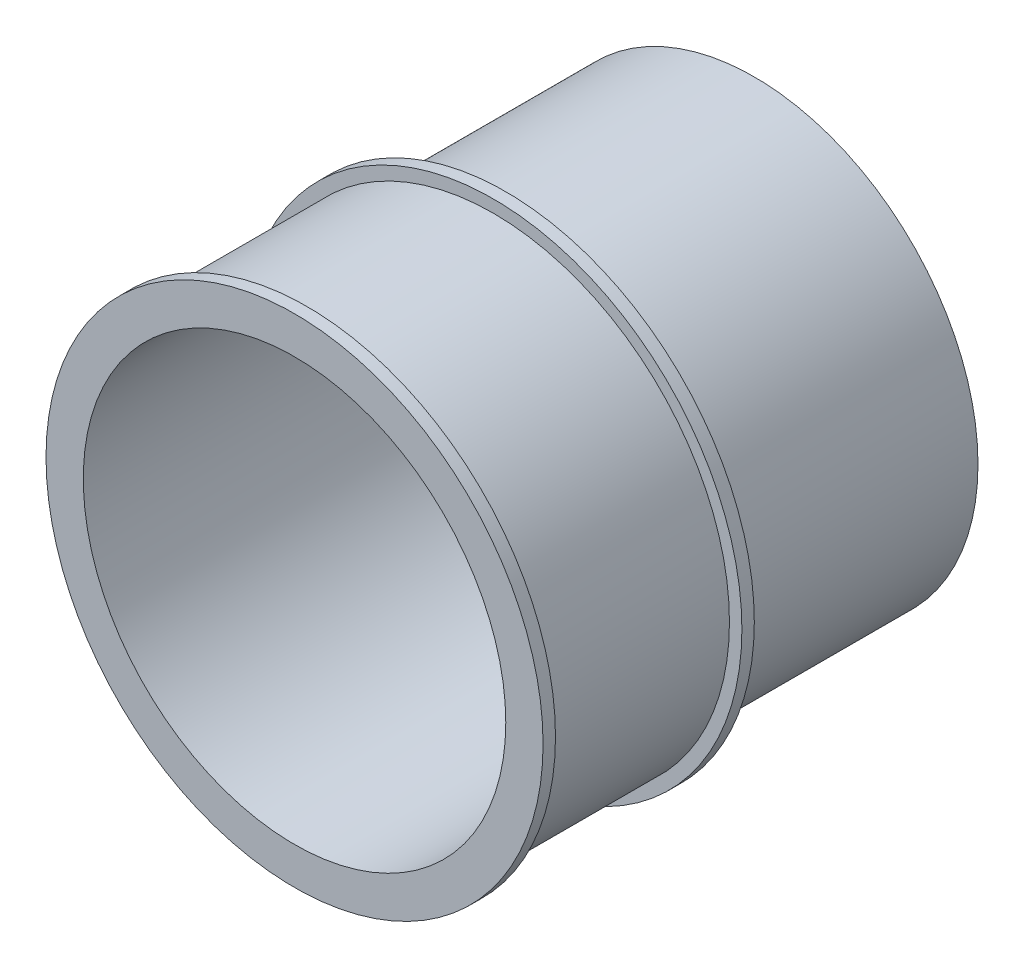
SolidWorks part; units mm, degrees
ref_plane "前视基准面" through (0, 0, 0) normal (0, 0, 1) x (1, 0, 0)
ref_plane "上视基准面" through (0, 0, 0) normal (0, 1, 0) x (1, 0, 0)
ref_plane "右视基准面" through (0, 0, 0) normal (1, 0, 0) x (0, 0, -1)
other "Configuration Table"
sketch "草图1" plane through (0, 0, 0) normal (0, 0, 1) x (1, 0, 0)
  circle A0 centre (0, 0) radius 38
  circle A1 centre (0, 0) radius 36
  dimension "D1" = 2
extrude "凸台-拉伸1" add sketch "草图1" along normal blind 34
sketch "草图2" plane through (0, 0, 34) normal (0, 0, 1) x (1, 0, 0)
  circle A1 centre (0, 0) radius 38 construction
  circle A2 centre (0, 0) radius 40
  circle A3 centre (0, 0) radius 40
  circle A4 centre (0, 0) radius 38
  dimension "D1" = 2
extrude "凸台-拉伸2" add sketch "草图2" against normal blind 2
extrude "凸台-拉伸3" add sketch "草图2<2>" along normal blind 2 from surface starting at face at (38, 0, 0)
sketch "草图2<2>" plane through (0, 0, 34) normal (0, 0, 1) x (1, 0, 0) same geometry as "草图2"
sketch "草图3" plane through (0, 0, 0) normal (0, 0, -1) x (-1, 0, 0)
  circle A1 centre (0, 0) radius 36 construction
  circle A2 centre (0, 0) radius 34
  circle A3 centre (0, 0) radius 34
  circle A4 centre (0, 0) radius 36
  dimension "D1" = 2
extrude "凸台-拉伸4" add sketch "草图3" along normal blind 40 separate body
sketch "草图4" plane through (0, 0, -40) normal (0, 0, -1) x (-1, 0, 0)
  circle A0 centre (0, 0) radius 34 construction
  circle A1 centre (0, 0) radius 34
extrude "凸台-拉伸5" add sketch "草图4" against normal blind 2
sketch "草图5" plane through (0, 0, -40) normal (0, 0, -1) x (-1, 0, 0)
  circle A0 centre (0, 0) radius 5
extrude "切除-拉伸1" cut sketch "草图5" against normal through all both
sketch "草图6" plane through (0, 0, 0) normal (0, 0, 1) x (1, 0, 0)
  circle A0 centre (0, 0) radius 34 construction
  circle A1 centre (0, 0) radius 34
extrude "凸台-拉伸6" add sketch "草图6" along normal blind 2 from offset 30 offset against normal yes
sketch "草图7" plane through (0, 0, -28) normal (0, 0, 1) x (1, 0, 0)
  line L0 (0, 7) -> (12, 7)
  line L1 (0, 5) -> (10, 5)
  line L2 (10, 5) -> (10, -5)
  line L3 (10, -5) -> (-10, -5)
  line L4 (-10, -5) -> (-10, 5)
  line L5 (-10, 5) -> (0, 5)
  line L6 (12, 7) -> (12, -7)
  line L7 (12, -7) -> (-12, -7)
  line L8 (-12, -7) -> (-12, 7)
  line L9 (-12, 7) -> (0, 7)
  dimension "D1" = 2
extrude "凸台-拉伸7" add sketch "草图7" along normal blind 10
sketch "草图8" plane through (0, 0, 0) normal (0, 0, 1) x (1, 0, 0)
  circle A1 centre (0, 0) radius 36
  circle A2 centre (0, 0) radius 36
  circle M2 centre (0, 0) radius 36
  circle M3 centre (0, 0) radius 34
  dimension "D1" = 0
extrude "凸台-拉伸9" add sketch "草图8" along normal through all contours M2 M3 region at (-34.9818, 0, 0)
